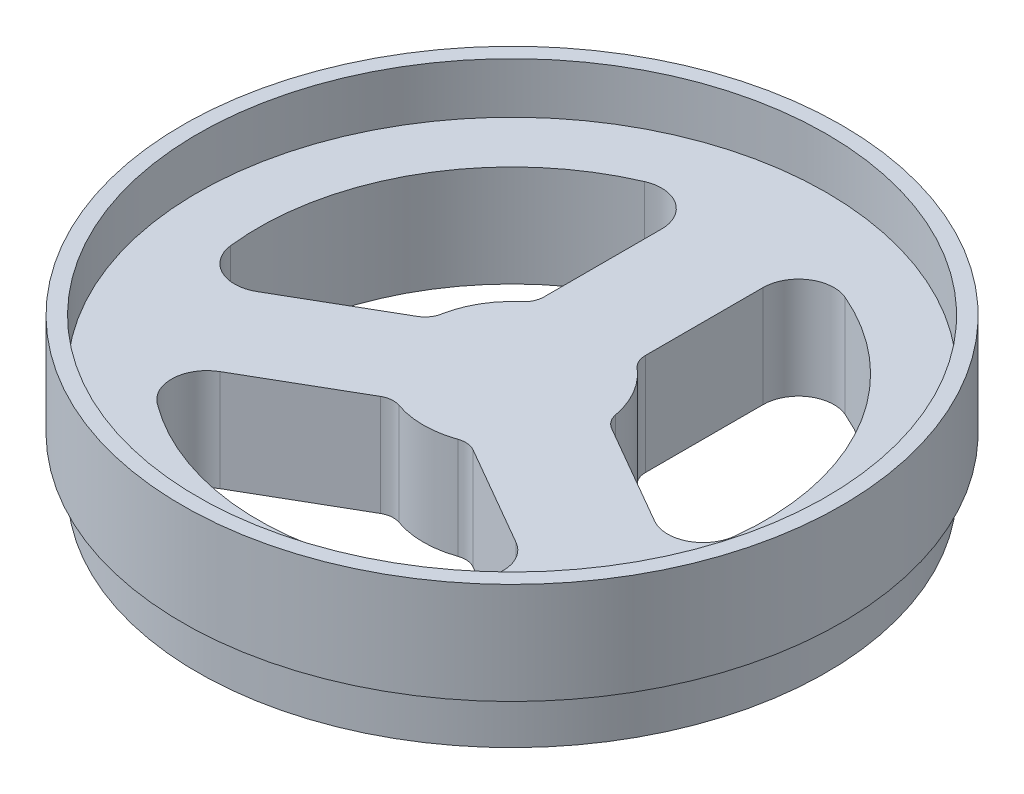
SolidWorks part; units mm, degrees
material "HYPALON"
ref_plane "Front Plane" through (0, 0, 0) normal (0, 0, 1) x (1, 0, 0)
ref_plane "Top Plane" through (0, 0, 0) normal (0, 1, 0) x (1, 0, 0)
ref_plane "Right Plane" through (0, 0, 0) normal (1, 0, 0) x (0, 0, -1)
sketch "Sketch1" plane through (0, 0, 0) normal (0, 0, 1) x (1, 0, 0)
  line L0 (0, 0) -> (0, 22.2877) construction
  line L1 (0, 0) -> (-62, 0)
  line L2 (-62, 0) -> (-62, 10)
  line L3 (-62, 10) -> (-65, 10)
  line L4 (-65, 10) -> (-65, 30)
  line L5 (-65, 30) -> (-62, 30)
  line L6 (-62, 30) -> (-62, 20)
  line L7 (-62, 20) -> (0, 20)
  line L8 (0, 20) -> (0, 0)
  point P3 (-62, 25)
  point P11 (0, 0)
  dimension "D1" = 20
  dimension "D2" = 10
  dimension "D3" = 10
  dimension "D4" = 3
  dimension "D5" = 65
  dimension "D6" = 3
revolve "Revolve1" add sketch "Sketch1" angle 360 about L0
sketch "Szkic1" plane through (0, 0, 0) normal (0, 1, 0) x (1, 0, 0)
  line L0 (0, 0) -> (-10, 0)
  line L1 (-10, 0) -> (0, 0)
  line L2 (0, 0) -> (10, 0)
  line L3 (-10, 0) -> (-10, 14.3614)
  line L4 (10, 0) -> (10, 14.3614)
  line L5 (7.4373, -15.841) -> (37.4264, -33.1552)
  line L6 (-10, 14.3614) -> (-10, 48.9898)
  line L7 (10, 14.3614) -> (10, 48.9898)
  line L8 (17.4373, 1.4796) -> (47.4264, -15.8346)
  line L9 (-17.4373, 1.4796) -> (-47.4264, -15.8346)
  line L10 (-7.4373, -15.841) -> (-37.4264, -33.1552)
  circle A0 centre (0, 0) radius 64
  circle A1 centre (0, 0) radius 50
  circle A2 centre (0, 0) radius 17.5
  point P22 (0, 0)
  dimension "D1" = 128
  dimension "D2" = 100
  dimension "D5" = 35
  dimension "D3" = 10
  dimension "D4" = 10
  dimension "D6" = 3
sketch "Szkic2" plane through (0, 0, 0) normal (0, 1, 0) x (1, 0, 0)
  circle A0 centre (0, 0) radius 35
  circle A1 centre (0, 0) radius 63
  dimension "D1" = 126
  dimension "D2" = 70
extrude "Cut-Extrude1" cut sketch "Szkic1" along normal up to surface (20 mm away) contours A2 L6 A1 L9 | A2 L8 A1 L7 | A2 L10 A1 L5 region at (-29.26, 0, -16.8933) region at (29.26, 0, -16.8933) region at (0, 0, 33.7865) up to face at (0, 20, -62)
fillet "Fillet1" radius 4 6 edges at (-17.4373, 10, -1.4796) (-10, 10, -14.3614) (10, 10, -14.3614) (17.4373, 10, -1.4796) (7.4373, 10, 15.841) (-7.4373, 10, 15.841)
fillet "Fillet2" radius 7 6 edges at (37.4264, 10, 33.1552) (47.4264, 10, 15.8346) (10, 10, -48.9898) (-10, 10, -48.9898) (-47.4264, 10, 15.8346) (-37.4264, 10, 33.1552)
